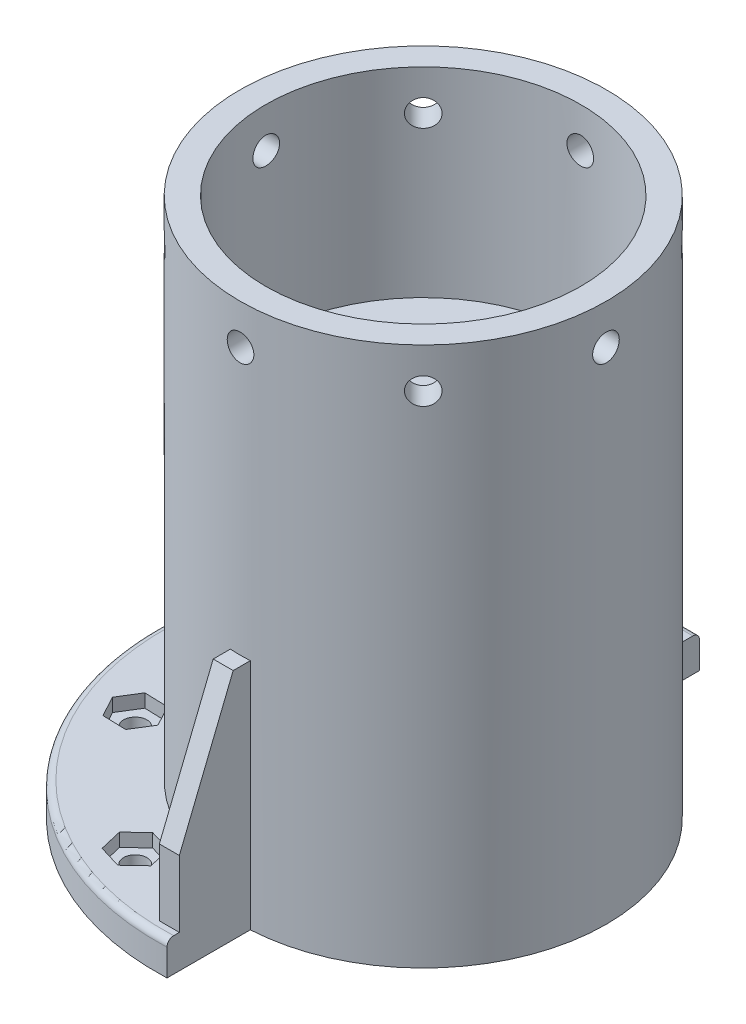
SolidWorks part; units mm, degrees
ref_plane "Front Plane" through (0, 0, 0) normal (0, 0, 1) x (1, 0, 0)
ref_plane "Top Plane" through (0, 0, 0) normal (0, 1, 0) x (1, 0, 0)
ref_plane "Right Plane" through (0, 0, 0) normal (1, 0, 0) x (0, 0, -1)
sketch "Sketch1" plane through (0, 0, 0) normal (0, 1, 0) x (1, 0, 0)
  circle A0 centre (0, 0) radius 23.65
  circle A1 centre (0, 0) radius 27.5
  dimension "D1" = 47.3
  dimension "D2" = 55
extrude "Boss-Extrude1" add sketch "Sketch1" along normal blind 30
sketch "Sketch2" plane through (0, 0, 0) normal (0, 0, 1) x (1, 0, 0)
  line L0 (27.5, 30) -> (-27.5, 30) construction
  circle A0 centre (0, 24) radius 2
  dimension "D2" = 4
  dimension "D1" = 6
extrude "Cut-Extrude1" cut sketch "Sketch2" against normal through all both and the other way through all
pattern_circular "CirPattern1" count 4 every 45 about axis through (0, 30, 0) along (0, 1, 0) of "Cut-Extrude1"
sketch "Sketch3" plane through (0, 0, 0) normal (0, -1, 0) x (1, 0, 0)
  circle A0 centre (0, 0) radius 27.5
extrude "Boss-Extrude2" add sketch "Sketch3" along normal blind 51
sketch "Sketch4" plane through (0, -51, 0) normal (0, -1, 0) x (1, 0, 0)
  line L0 (1.5, 39.9719) -> (1.5, -39.9719)
  arc A0 (1.5, 39.9719) -> (1.5, -39.9719) centre (0, 0) ccw
  point P1 (1.5, -39.5716)
  point P5 (1.5, -40.8839)
  circle M1 centre (0, 0) radius 27.5
  dimension "D1" = 80
  dimension "D2" = 1.5
extrude "Boss-Extrude3" add sketch "Sketch4" against normal blind 5 contours L0 A0 M1 | L0 M1 region at (0.5988, -51, 33.7155) region at (-10.8651, -51, 0)
sketch "Sketch6" plane through (0, -46, 0) normal (0, 1, 0) x (1, 0, 0)
  line L0 (1.5, 27.4591) -> (1.5, 39.9719) construction
  line L1 (1.5, 36.6445) -> (-1.5, 36.6445)
  line L2 (1.5, 36.6445) -> (1.5, 24.6445)
  line L3 (1.5, 24.6445) -> (-1.5, 24.6445)
  line L4 (-1.5, 36.6445) -> (-1.5, 24.6445)
  line L5 (1.5, -39.9719) -> (1.5, -27.4591) construction
  line L6 (-36.7098, 1.2195) -> (-24.7098, 1.2195)
  line L7 (-36.7098, 1.2195) -> (-36.7098, -1.7805)
  line L8 (-36.7098, -1.7805) -> (-24.7098, -1.7805)
  line L9 (-24.7098, 1.2195) -> (-24.7098, -1.7805)
  line L10 (1.5, -38.1145) -> (-1.5, -38.1145)
  line L11 (1.5, -38.1145) -> (1.5, -26.1145)
  line L12 (1.5, -26.1145) -> (-1.5, -26.1145)
  line L13 (-1.5, -38.1145) -> (-1.5, -26.1145)
  dimension "D1" = 3
  dimension "D2" = 12
  dimension "D3" = 12
  dimension "D4" = 3
  dimension "D5" = 3
  dimension "D6" = 12
extrude "Boss-Extrude4" add sketch "Sketch6" along normal blind 30
chamfer "Chamfer1" distance 20 angle 22 3 edges at (0, -16, -36.6445) (-36.7098, -16, 0.2805) (0, -16, 38.1145) first distance on face at (0, -31, -36.6445) first distance on face at (-36.7098, -31, 0.2805) first distance on face at (0, -31, 38.1145)
sketch "Sketch7" plane through (0, -46, 0) normal (0, 1, 0) x (1, 0, 0)
  line L0 (0, 0) -> (-12.6635, 30.5724) construction
  line L1 (1.5, 36.6445) -> (1.5, 39.9719) construction
  circle A0 centre (-12.6635, 30.5724) radius 1.75
  dimension "D1" = 3.5
  dimension "D2" = 22.5
extrude "Cut-Extrude2" cut sketch "Sketch7" against normal through all
sketch "Sketch8" plane through (0, -46, 0) normal (0, 1, 0) x (1, 0, 0)
  line L1 (-9.5616, 32.2402) -> (-12.5569, 34.0926)
  line L2 (-12.5569, 34.0926) -> (-15.6588, 32.4249)
  line L3 (-15.6588, 32.4249) -> (-15.7654, 28.9046)
  line L4 (-15.7654, 28.9046) -> (-12.7701, 27.0522)
  line L5 (-12.7701, 27.0522) -> (-9.6682, 28.72)
  line L6 (-9.6682, 28.72) -> (-9.5616, 32.2402)
  circle A0 centre (-12.6635, 30.5724) radius 3.05 construction
  dimension "D1" = 6.1
extrude "Cut-Extrude3" cut sketch "Sketch8" against normal blind 2
pattern_circular "CirPattern2" count 4 every 45 about axis through (0, -46, 0) along (0, -1, 0) of "Cut-Extrude2", "Cut-Extrude3" reverse direction yes
fillet "Fillet1" radius 1 1 edges at (-40, -46, 0)
